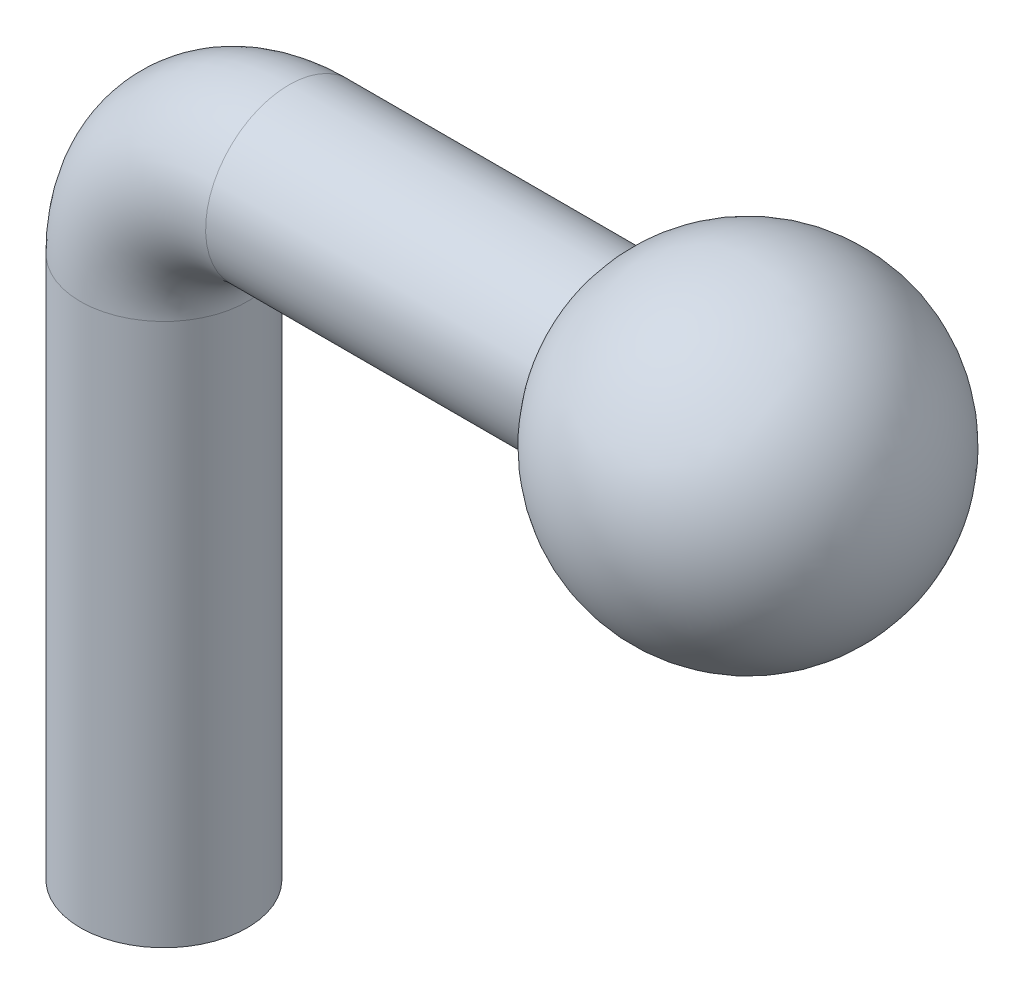
SolidWorks part; units mm, degrees
ref_plane "Front Plane" through (0, 0, 0) normal (0, 0, 1) x (1, 0, 0)
ref_plane "Top Plane" through (0, 0, 0) normal (0, 1, 0) x (1, 0, 0)
ref_plane "Right Plane" through (0, 0, 0) normal (1, 0, 0) x (0, 0, -1)
sketch "Sketch1" plane through (0, 0, 0) normal (0, 1, 0) x (1, 0, 0)
  circle A0 centre (0, 0) radius 2
  dimension "D1" = 4
sketch "Sketch3" plane through (0, 0, 0) normal (0, 0, 1) x (1, 0, 0)
  line L0 (0, 0) -> (0, 13)
  line L1 (3, 16) -> (14, 16)
  arc A0 (0, 13) -> (3, 16) centre (3, 13) cw
  point P6 (0, 16)
  dimension "D3" = 3
  dimension "D1" = 16
  dimension "D2" = 14
sweep "Sweep1" add profiles "Sketch1" path "Sketch3"
sketch "Sketch4" plane through (0, 0, 0) normal (0, 0, 1) x (1, 0, 0)
  line L0 (14, 14) -> (14, 18) construction
  line L1 (10.1, 16) -> (17.9, 16)
  circle A0 centre (14, 16) radius 3.9
  dimension "D1" = 7.8
revolve "Revolve1" add sketch "Sketch4" angle 360 about L1 region at (14, 17.6552, 0)
